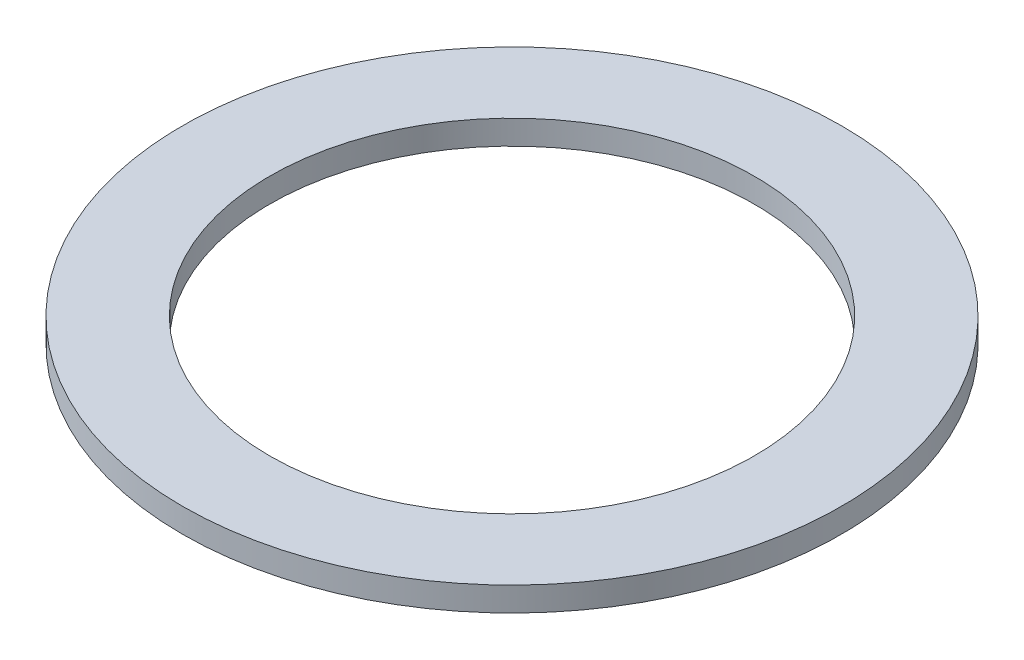
SolidWorks part; units mm, degrees
material "Alum Plate"
ref_plane "Front Plane" through (0, 0, 0) normal (0, 0, 1) x (1, 0, 0)
ref_plane "Top Plane" through (0, 0, 0) normal (0, 1, 0) x (1, 0, 0)
ref_plane "Right Plane" through (0, 0, 0) normal (1, 0, 0) x (0, 0, -1)
other "Bounding Box"
ref_plane "Default Plane" through (-8.9266, -12.7485, 0) normal (-0.1736, 0.9848, 0) x (0.9848, 0.1736, 0)
sketch "Sketch1" plane through (0, 0, 0) normal (0, 1, 0) x (1, 0, 0)
  circle A0 centre (0, 0) radius 12.7
  circle A1 centre (0, 0) radius 17.272
  dimension "D1" = 25.4
  dimension "D2" = 34.544
extrude "Boss-Extrude1" add sketch "Sketch1" along normal mid plane 1.27
